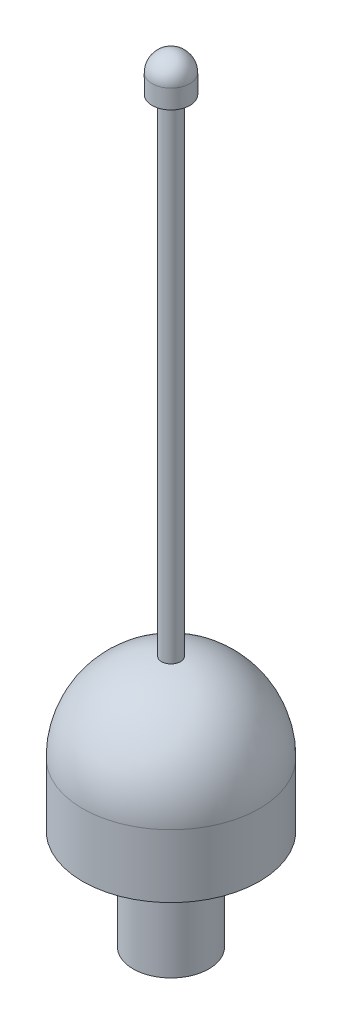
SolidWorks part; units mm, degrees
material "ABS"
ref_plane "Front Plane" through (0, 0, 0) normal (0, 0, 1) x (1, 0, 0)
ref_plane "Top Plane" through (0, 0, 0) normal (0, 1, 0) x (1, 0, 0)
ref_plane "Right Plane" through (0, 0, 0) normal (1, 0, 0) x (0, 0, -1)
sketch "Sketch1" plane through (0, 0, 0) normal (0, 0, 1) x (1, 0, 0)
  line L0 (0, 39.0525) -> (0, -2.3663) construction
  line L1 (0, 0) -> (1.905, 0)
  line L2 (1.905, 0) -> (1.905, 11.5546)
  line L3 (0.4763, 37.1475) -> (0.9525, 37.1475)
  line L4 (0.9525, 37.1475) -> (0.9525, 38.1)
  line L5 (0.4763, 37.1475) -> (0.4763, 12.6744)
  line L6 (4.445, 5.08) -> (3.81, 5.08)
  line L7 (4.445, 5.08) -> (4.445, 8.255)
  line L8 (0, 0) -> (0, 39.0525)
  line L9 (3.81, 5.08) -> (3.81, 8.255)
  arc A0 (0.9525, 38.1) -> (0, 39.0525) centre (0, 38.1) ccw
  arc A3 (4.445, 8.255) -> (0.4763, 12.6744) centre (0, 8.255) ccw
  arc A4 (3.81, 8.255) -> (1.905, 11.5546) centre (0, 8.255) ccw
  arc A5 (3.81, 8.255) -> (0.4082, 12.0431) centre (0, 8.255) ccw construction
  dimension "D2" = 1.905
  dimension "D1" = 0.635
  dimension "D7" = 3.175
revolve "Revolve1" add sketch "Sketch1" angle 360 about L0
